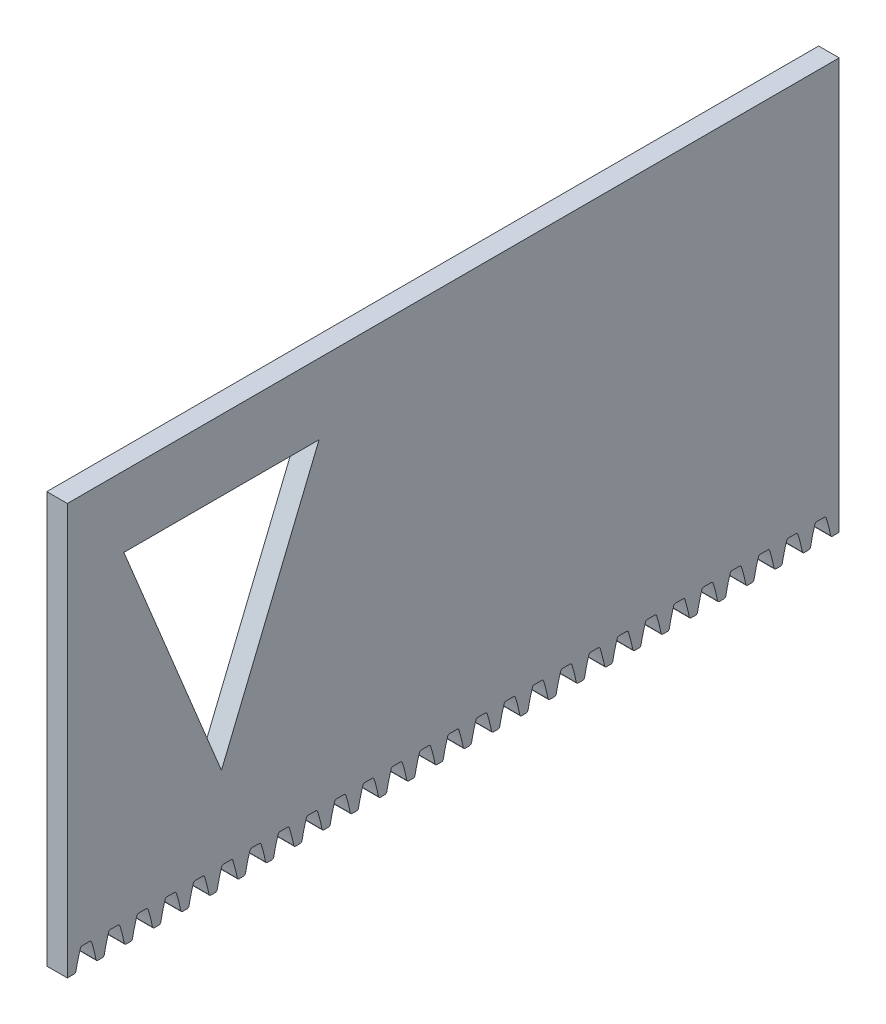
SolidWorks part; units mm, degrees
ref_plane "Front Plane" through (0, 0, 0) normal (0, 0, 1) x (1, 0, 0)
ref_plane "Top Plane" through (0, 0, 0) normal (0, 1, 0) x (1, 0, 0)
ref_plane "Right Plane" through (0, 0, 0) normal (1, 0, 0) x (0, 0, -1)
sketch "Sketch1" plane through (0, 0, 0) normal (1, 0, 0) x (0, 0, -1)
  line L0 (0, 0) -> (0, 118.8855) construction
  line L4 (-20, 0) -> (20, 0)
  line L5 (-37.5648, 40) -> (-37.5648, 0)
  line L6 (-37.5648, 0) -> (-20, 0)
  line L7 (37.5648, 40) -> (37.5648, 0)
  line L8 (37.5648, 0) -> (20, 0)
  line L9 (-37.5648, 40) -> (37.5648, 40)
  dimension "D1" = 40
extrude "Boss-Extrude1" add sketch "Sketch1" along normal blind 2
sketch "Sketch2" plane through (0, 0, 0) normal (-1, 0, 0) x (0, 0, 1)
  line L0 (22.5648, 10) -> (22.5648, 33.1247) construction
  line L1 (37.5648, 40) -> (37.5648, 0) construction
  line L2 (37.5648, 0) -> (-37.5648, 0) construction
  line L3 (22.5648, 10) -> (13.0648, 33.1247)
  line L4 (13.0648, 33.1247) -> (32.0648, 33.1247)
  line L5 (32.0648, 33.1247) -> (22.5648, 10)
  dimension "D1" = 15
  dimension "D2" = 10
  dimension "D3" = 25
  dimension "D4" = 25
  dimension "D5" = 19
extrude "Cut-Extrude1" cut sketch "Sketch2" against normal through all
sketch "Sketch3" plane through (0, 0, 0) normal (-1, 0, 0) x (0, 0, 1)
  line L0 (0, 0) -> (0, 85.2855) construction
  line L1 (-0.5, 2) -> (0.5, 2)
  line L2 (37.5648, 0) -> (-37.5648, 0) construction
  line L5 (-1, 0) -> (1, 0)
  arc A0 (-0.5, 2) -> (-1, 0) centre (13.7677, -2.6294) ccw
  arc A1 (0.5, 2) -> (1, 0) centre (-13.7677, -2.6294) cw
  point P7 (0, 2)
  dimension "D1" = 15
  dimension "D2" = 2
  dimension "D3" = 1
  dimension "D4" = 2
extrude "Cut-Extrude2" cut sketch "Sketch3" against normal through all
fillet "Fillet1" radius 0.2 4 edges at (1, 2, -0.5) (1, 2, 0.5) (1, 0, 1) (1, 0, -1)
pattern_linear "LPattern1" count 14 spacing 2.75 along (0, 0, 1) count 14 spacing 2.75 along (0, 0, -1) of "Cut-Extrude2", "Fillet1" pattern seed only yes
